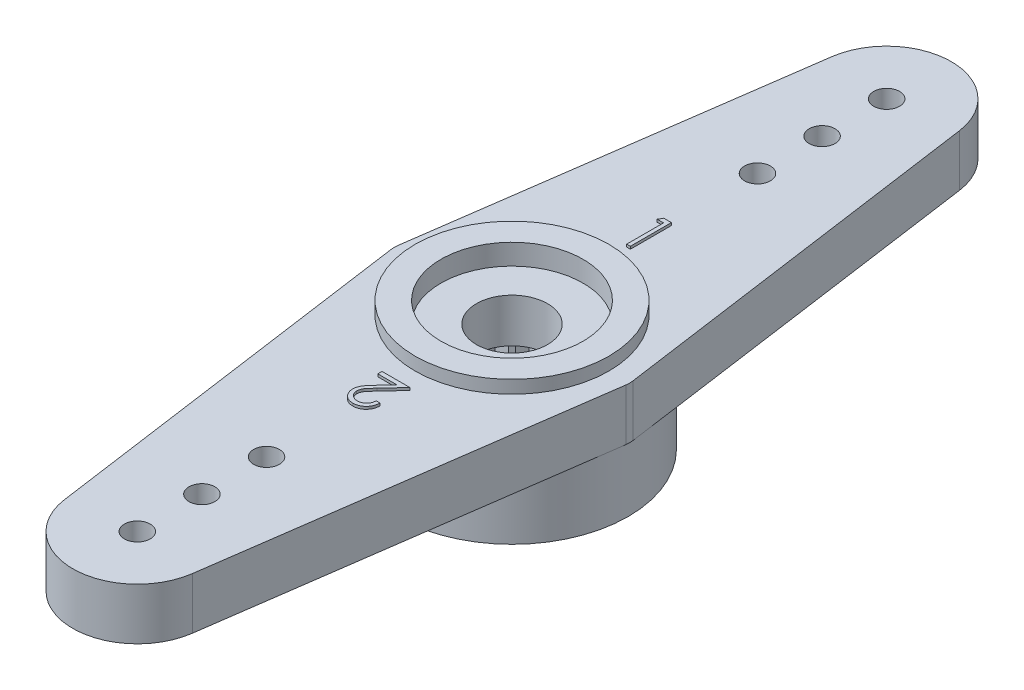
SolidWorks part; units mm, degrees
ref_plane "Front Plane" through (0, 0, 0) normal (0, 0, 1) x (1, 0, 0)
ref_plane "Top Plane" through (0, 0, 0) normal (0, 1, 0) x (1, 0, 0)
ref_plane "Right Plane" through (0, 0, 0) normal (1, 0, 0) x (0, 0, -1)
sketch "Sketch1" plane through (0, 0, 0) normal (0, 1, 0) x (1, 0, 0)
  line L0 (0, 17) -> (0, -17) construction
  line L1 (-17, 0) -> (17, 0) construction
  line L2 (-2.6883, 13.3345) -> (-4.0139, 3.9009) construction
  line L3 (4, -4) -> (-4, -4) construction
  line L4 (4, -4) -> (4, 4) construction
  line L5 (4, 4) -> (-4, 4) construction
  line L6 (-4, -4) -> (-4, 4) construction
  line L7 (4, -4) -> (-4, 4) construction
  line L8 (4, 4) -> (-4, -4) construction
  line L9 (-4, 4) -> (-2.4757, 14.8479)
  line L10 (4, 4) -> (2.4757, 14.8479)
  line L11 (4, -4) -> (2.4757, -14.8479)
  line L12 (-4, -4) -> (-2.4757, -14.8479)
  line L13 (-4, 4) -> (-4.5621, 0)
  line L14 (4, 4) -> (4.5621, 0)
  line L15 (4, -4) -> (4.5621, 0)
  line L16 (-4, -4) -> (-4.5621, 0)
  circle A0 centre (0, 0) radius 17 construction
  circle A1 centre (0, 0) radius 16 construction
  arc A2 (2.4757, 14.8479) -> (-2.4757, 14.8479) centre (0, 14.5) ccw
  arc A3 (2.4757, -14.8479) -> (-2.4757, -14.8479) centre (0, -14.5) cw
  circle A4 centre (0, -9.5) radius 0.5
  circle A5 centre (0, -12) radius 0.5
  circle A6 centre (0, 0) radius 14.5 construction
  circle A7 centre (0, 0) radius 12 construction
  circle A8 centre (0, 0) radius 9.5 construction
  circle A9 centre (0, 14.5) radius 0.5
  circle A10 centre (0, 12) radius 0.5
  circle A11 centre (0, 9.5) radius 0.5
  circle A12 centre (0, -14.5) radius 0.5
  circle A21 centre (0, 0) radius 1.375
  point P13 (-4.5621, 0)
  point P59 (0, 0)
  dimension "D1" = 34
  dimension "D2" = 1
  dimension "D3" = 5
  dimension "D4" = 24
  dimension "D5" = 8
  dimension "D6" = 8
  dimension "D7" = 19
  dimension "D9" = 29
  dimension "D11" = 1
  dimension "D12" = 1
  dimension "D13" = 1
  dimension "D8" = 1
  dimension "D10" = 1
  dimension "D14" = 2.75
  dimension "D15" = 1
extrude "Boss-Extrude1" add sketch "Sketch1" along normal blind 2
sketch "Sketch2" plane through (0, 2, 0) normal (0, 1, 0) x (1, 0, 0)
  circle A0 centre (0, 0) radius 3.75
  circle A1 centre (0, 0) radius 2.75
  dimension "D1" = 7.5
  dimension "D2" = 1
extrude "Boss-Extrude2" add sketch "Sketch2" along normal blind 0.5
sketch "Sketch3" plane through (0, 2.5, 0) normal (0, 1, 0) x (1, 0, 0)
  circle A2 centre (0, 0) radius 1.375
  circle A3 centre (0, 0) radius 2.75
  circle A5 centre (0, 0) radius 2.75
  circle A6 centre (0, 0) radius 2.75
  circle M6 centre (0, 0) radius 2.75
  dimension "D1" = 0
extrude "Cut-Extrude1" cut sketch "Sketch3" against normal blind 0.8 contours A2 M6 region at (-2.6722, 2.5, 0)
sketch "Sketch4" plane through (0, 0, 0) normal (0, -1, 0) x (1, 0, 0)
  circle A0 centre (0, 0) radius 4.5
  circle A1 centre (0, 0) radius 2.5
  dimension "D1" = 9
  dimension "D2" = 2
extrude "Boss-Extrude3" add sketch "Sketch4" along normal blind 2.5
sketch "Sketch5" plane through (0, -2.5, 0) normal (0, -1, 0) x (1, 0, 0)
  line L0 (0, 0) -> (0, 0.6245) construction
  line L1 (0, 3) -> (-0.299, 2.4821)
  line L2 (0, 3) -> (0.299, 2.4821)
  line L3 (0.9271, 2.8532) -> (0.4826, 2.453)
  line L4 (0.9271, 2.8532) -> (1.0514, 2.2682)
  line L5 (1.7634, 2.4271) -> (1.217, 2.1838)
  line L6 (1.7634, 2.4271) -> (1.7008, 1.8323)
  line L7 (2.4271, 1.7634) -> (1.8323, 1.7008)
  line L8 (2.4271, 1.7634) -> (2.1838, 1.217)
  line L9 (2.8532, 0.9271) -> (2.2682, 1.0514)
  line L10 (2.8532, 0.9271) -> (2.453, 0.4826)
  line L11 (3, 0) -> (2.4821, 0.299)
  line L12 (3, 0) -> (2.4821, -0.299)
  line L13 (2.8532, -0.9271) -> (2.453, -0.4826)
  line L14 (2.8532, -0.9271) -> (2.2682, -1.0514)
  line L15 (2.4271, -1.7634) -> (2.1838, -1.217)
  line L16 (2.4271, -1.7634) -> (1.8323, -1.7008)
  line L17 (1.7634, -2.4271) -> (1.7008, -1.8323)
  line L18 (1.7634, -2.4271) -> (1.217, -2.1838)
  line L19 (0.9271, -2.8532) -> (1.0514, -2.2682)
  line L20 (0.9271, -2.8532) -> (0.4826, -2.453)
  line L21 (0, -3) -> (0.299, -2.4821)
  line L22 (0, -3) -> (-0.299, -2.4821)
  line L23 (-0.9271, -2.8532) -> (-0.4826, -2.453)
  line L24 (-0.9271, -2.8532) -> (-1.0514, -2.2682)
  line L25 (-1.7634, -2.4271) -> (-1.217, -2.1838)
  line L26 (-1.7634, -2.4271) -> (-1.7008, -1.8323)
  line L27 (-2.4271, -1.7634) -> (-1.8323, -1.7008)
  line L28 (-2.4271, -1.7634) -> (-2.1838, -1.217)
  line L29 (-2.8532, -0.9271) -> (-2.2682, -1.0514)
  line L30 (-2.8532, -0.9271) -> (-2.453, -0.4826)
  line L31 (-3, 0) -> (-2.4821, -0.299)
  line L32 (-3, 0) -> (-2.4821, 0.299)
  line L33 (-2.8532, 0.9271) -> (-2.453, 0.4826)
  line L34 (-2.8532, 0.9271) -> (-2.2682, 1.0514)
  line L35 (-2.4271, 1.7634) -> (-2.1838, 1.217)
  line L36 (-2.4271, 1.7634) -> (-1.8323, 1.7008)
  line L37 (-1.7634, 2.4271) -> (-1.7008, 1.8323)
  line L38 (-1.7634, 2.4271) -> (-1.217, 2.1838)
  line L39 (-0.9271, 2.8532) -> (-1.0514, 2.2682)
  line L40 (-0.9271, 2.8532) -> (-0.4826, 2.453)
  circle A0 centre (0, 0) radius 2.5 construction
  arc A1 (-2.1838, 1.217) -> (-2.2682, 1.0514) centre (0, 0) ccw
  arc A2 (-1.7008, 1.8323) -> (-1.8323, 1.7008) centre (0, 0) ccw
  arc A3 (-1.0514, 2.2682) -> (-1.217, 2.1838) centre (0, 0) ccw
  arc A4 (-0.299, 2.4821) -> (-0.4826, 2.453) centre (0, 0) ccw
  arc A5 (0.4826, 2.453) -> (0.299, 2.4821) centre (0, 0) ccw
  arc A6 (1.217, 2.1838) -> (1.0514, 2.2682) centre (0, 0) ccw
  arc A7 (1.8323, 1.7008) -> (1.7008, 1.8323) centre (0, 0) ccw
  arc A8 (2.2682, 1.0514) -> (2.1838, 1.217) centre (0, 0) ccw
  arc A9 (2.4821, 0.299) -> (2.453, 0.4826) centre (0, 0) ccw
  arc A10 (2.453, -0.4826) -> (2.4821, -0.299) centre (0, 0) ccw
  arc A11 (2.1838, -1.217) -> (2.2682, -1.0514) centre (0, 0) ccw
  arc A12 (1.7008, -1.8323) -> (1.8323, -1.7008) centre (0, 0) ccw
  arc A13 (1.0514, -2.2682) -> (1.217, -2.1838) centre (0, 0) ccw
  arc A14 (0.299, -2.4821) -> (0.4826, -2.453) centre (0, 0) ccw
  arc A15 (-0.4826, -2.453) -> (0, -2.5) centre (0, 0) ccw
  arc A16 (-1.217, -2.1838) -> (-1.0514, -2.2682) centre (0, 0) ccw
  arc A17 (-1.8323, -1.7008) -> (-1.7008, -1.8323) centre (0, 0) ccw
  arc A18 (-2.2682, -1.0514) -> (-2.1838, -1.217) centre (0, 0) ccw
  arc A19 (-2.4821, -0.299) -> (-2.453, -0.4826) centre (0, 0) ccw
  arc A20 (-2.453, 0.4826) -> (-2.4821, 0.299) centre (0, 0) ccw
  point P68 (0, 0)
  circle M5 centre (0, 0) radius 2.5
  dimension "D1" = 30
  dimension "D2" = 3
  dimension "D3" = 20
extrude "Cut-Extrude3" cut sketch "Sketch5" against normal up to surface (2.5 mm away) contours L36 L35 M5 | L34 L33 M5 | L32 L31 M5 | L30 L29 M5 | L28 L27 M5 | L26 L25 M5 | L24 L23 M5 | L0 L21 M5 | L22 L0 M5 | L20 L19 M5 | L18 L17 M5 | L16 L15 M5 | L14 L13 M5 | L12 L11 M5 | L10 L9 M5 | L8 L7 M5 | L6 L5 M5 | L4 L3 M5 | L0 L2 M5 | L0 L1 M5 | L40 L39 M5 | L38 L37 M5 region at (0, -2.5, 2.6627) region at (-0.8228, -2.5, 2.5324) region at (0.8228, -2.5, 2.5324) region at (-1.5651, -2.5, 2.1542) region at (1.5651, -2.5, 2.1542) region at (-2.1542, -2.5, 1.5651) region at (2.1542, -2.5, 1.5651) region at (-2.5324, -2.5, 0.8228) region at (2.5324, -2.5, 0.8228) region at (-2.6627, -2.5, 0) region at (2.6627, -2.5, 0) region at (-2.5324, -2.5, -0.8228) region at (2.5324, -2.5, -0.8228) region at (-2.1542, -2.5, -1.5651) region at (2.1542, -2.5, -1.5651) region at (-1.5651, -2.5, -2.1542) region at (1.5651, -2.5, -2.1542) region at (-0.8228, -2.5, -2.5324) region at (0.8228, -2.5, -2.5324) region at (0, -2.5, -2.6627) up to face at (0, 0, 1.375)
sketch "Sketch6" plane through (0, 2, 0) normal (0, 1, 0) x (1, 0, 0)
  line L1 (4.5, -4.5) -> (-4.5, -4.5) construction
  line L2 (4.5, -4.5) -> (4.5, 4.5) construction
  line L3 (4.5, 4.5) -> (-4.5, 4.5) construction
  line L4 (-4.5, -4.5) -> (-4.5, 4.5) construction
  line L5 (4.5, -4.5) -> (-4.5, 4.5) construction
  line L6 (4.5, 4.5) -> (-4.5, -4.5) construction
  circle A0 centre (0, 0) radius 4.5 construction
  text T0 "1" font "Century Gothic" height in points 6
  text T2 "2" font "Century Gothic" height in points 6
  dimension "D1" = 9
  dimension "D2" = 9
  dimension "D3" = 9
extrude "Boss-Extrude4" add sketch "Sketch6" along normal blind 0.1
fillet "Fillet1" radius 1 2 edges at (-4.5621, 1, 0) (4.5621, 1, 0)
